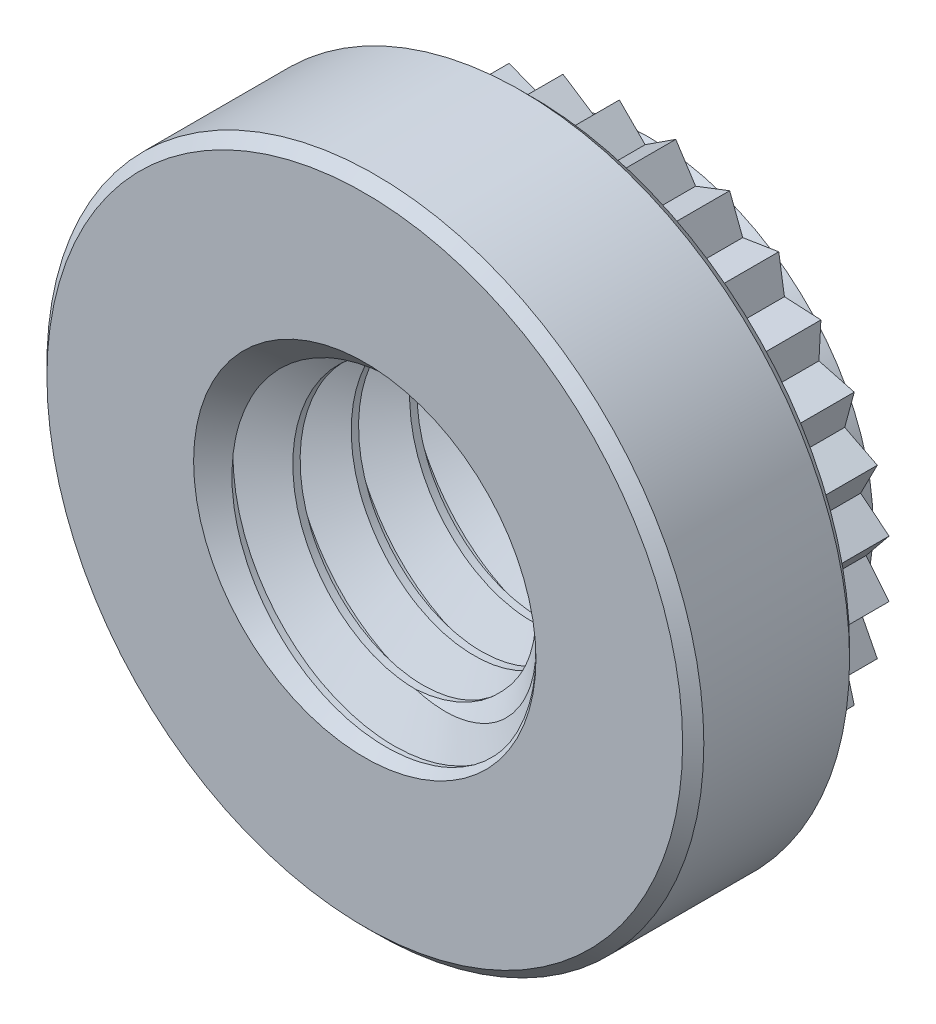
SolidWorks part; units mm, degrees
ref_plane "Front Plane" through (0, 0, 0) normal (0, 0, 1) x (1, 0, 0)
ref_plane "Top Plane" through (0, 0, 0) normal (0, 1, 0) x (1, 0, 0)
ref_plane "Right Plane" through (0, 0, 0) normal (1, 0, 0) x (0, 0, -1)
sketch "Sketch1" plane through (0, 0, 0) normal (0, 0, 1) x (1, 0, 0)
  circle A0 centre (0, 0) radius 3.935
  dimension "A" = 7.87
extrude "Extrude1" add sketch "Sketch1" against normal blind 2
sketch "Sketch15" plane through (0, 0, -2) normal (0, 0, -1) x (-1, 0, 0)
  circle A0 centre (0, 0) radius 2.7
  dimension "hole dia" = 5.4
sketch "Sketch2" plane through (0, 0, -2) normal (0, 0, -1) x (-1, 0, 0)
  circle A0 centre (0, 0) radius 2.7125
  dimension "D1" = 5.425
extrude "Extrude2" add sketch "Sketch2" along normal blind 1.4
sketch "Sketch3" plane through (0, 0, -3.4) normal (0, 0, -1) x (-1, 0, 0)
  line L0 (0, 2.522) -> (0, 3.935)
  circle A1 centre (0, 0) radius 3.935 construction
  circle A2 centre (0, 0) radius 2.522
  circle A3 centre (0, 0) radius 2.522 construction
  dimension "D1" = 0.1905
sketch "Sketch5" plane through (0, 0, -3.4) normal (0, 0, -1) x (-1, 0, 0)
  circle A0 centre (0, 0) radius 3.935 construction
  circle A3 centre (0, 0) radius 2.69
  dimension "C" = 5.38
extrude "Cut-Extrude1" cut sketch "Sketch5" against normal blind 0.35 draft 20 flip side to cut draft outward yes
chamfer "Chamfer2" distance 0.127 angle 45 2 edges at (3.935, 0, 0) (3.935, 0, -2)
sketch "Sketch7" plane through (0, 0, 0) normal (0, 0, 1) x (1, 0, 0)
  circle A0 centre (0, 0) radius 2
  dimension "Thread Od" = 4
extrude "Cut-Extrude3" cut sketch "Sketch7" against normal through all
sketch "Sketch8" plane through (0, 0, -3.4) normal (0, 0, -1) x (-1, 0, 0)
  circle A0 centre (0, 0) radius 2 construction
  circle A1 centre (0, 0) radius 2
curve "Helix/Spiral1" pitch 0.7 height 5.4 radius 2 centre (0, 0, -3.4) axis (0, 0, 1) start towards (0, 1, 0) parameters "pitch"=0.7
sketch "Sketch9" plane through (0, 0, 0) normal (1, 0, 0) x (0, 0, -1)
  line L0 (4.0125, 2) -> (3.75, 1.5453)
  line L1 (3.75, 1.5453) -> (3.6625, 1.5453)
  line L2 (3.6625, 1.5453) -> (3.4, 2)
  line L3 (4.0125, 2) -> (3.4, 2)
  line L4 (3.7062, 2) -> (3.7062, 1.5453) construction
  line L5 (3.8813, 1.7727) -> (3.5312, 1.7727) construction
  line L6 (3.4, -2) -> (3.4, 2) construction
  dimension "D1" = 60
  dimension "D2" = 0.0875
  dimension "D3" = 0.35
sweep "Sweep1" add profiles "Sketch9" path "Helix/Spiral1"
sketch "Sketch10" plane through (0, 0, 0) normal (0, 0, 1) x (1, 0, 0)
  circle A0 centre (0, 0) radius 3.935 construction
  circle A1 centre (0, 0) radius 3.935
extrude "Cut-Extrude4" cut sketch "Sketch10" along normal through all
sketch "Sketch11" plane through (0, 0, -3.4) normal (0, 0, -1) x (-1, 0, 0)
  circle A1 centre (0, 0) radius 2.69 construction
  circle A2 centre (0, 0) radius 2.69
extrude "Cut-Extrude5" cut sketch "Sketch11" along normal through all
sketch "Sketch13" plane through (0, 0, 0) normal (0, 0, 1) x (1, 0, 0)
  circle A2 centre (0, 0) radius 2.0508
  circle A3 centre (0, 0) radius 2.0508
  dimension "D1" = 0.0508
extrude "Cut-Extrude6" cut sketch "Sketch13" against normal through all draft 45
sketch "Sketch14" plane through (0, 0, -3.4) normal (0, 0, -1) x (-1, 0, 0)
  circle A2 centre (0, 0) radius 2.0635
  circle A3 centre (0, 0) radius 2.0635
  dimension "D1" = 0.0635
extrude "Cut-Extrude7" cut sketch "Sketch14" against normal through all draft 45
sketch "Sketch16" plane through (0, 0, -3.05) normal (0, 0, -1) x (-1, 0, 0)
  line L0 (0, 2.69) -> (0, 3.808) construction
  line L1 (0, 3.249) -> (-0.6028, 2.6447)
  line L2 (0, 3.249) -> (0.6028, 2.6447)
  circle A0 centre (0, 0) radius 2.5626 construction
  circle A1 centre (0, 0) radius 2.69 construction
  circle A2 centre (0, 0) radius 3.808 construction
  circle A3 centre (0, 0) radius 2.7125 construction
  arc A4 (-0.6028, 2.6447) -> (0.6028, 2.6447) centre (0, 0) cw
  circle A5 centre (0, 0) radius 2.7125 construction
  point P2 (0, 3.249)
  dimension "D2" = 1.2056
extrude "Boss-Extrude1" add sketch "Sketch16" against normal up to surface (1.05 mm away) up to face at (3.808, 0, -2)
pattern_circular "CirPattern4" count 30 over 360 about axis through (0, 0, -3.4) along (0, 0, -1) of "Boss-Extrude1"
equation "\"D3@Helix/Spiral1\"=\"B@Extrude1\"+\"panel min.@Extrude2\"+2"
equation "\"D2@Sketch9\" = \"pitch@Helix/Spiral1\"*.125"
equation "\"D3@Sketch9\" = \"pitch@Helix/Spiral1\"*.50"
equation "\"D1@Sketch2\" = \"hole dia@Sketch15\"+.025"
equation "\"D1@Cut-Extrude1\" = \"panel min.@Extrude2\"*.25"
equation "\"D2@Sketch16\"=\"D1@Sketch2\"/4.5"
equation "\"D1@CirPattern4\"=360/12"
